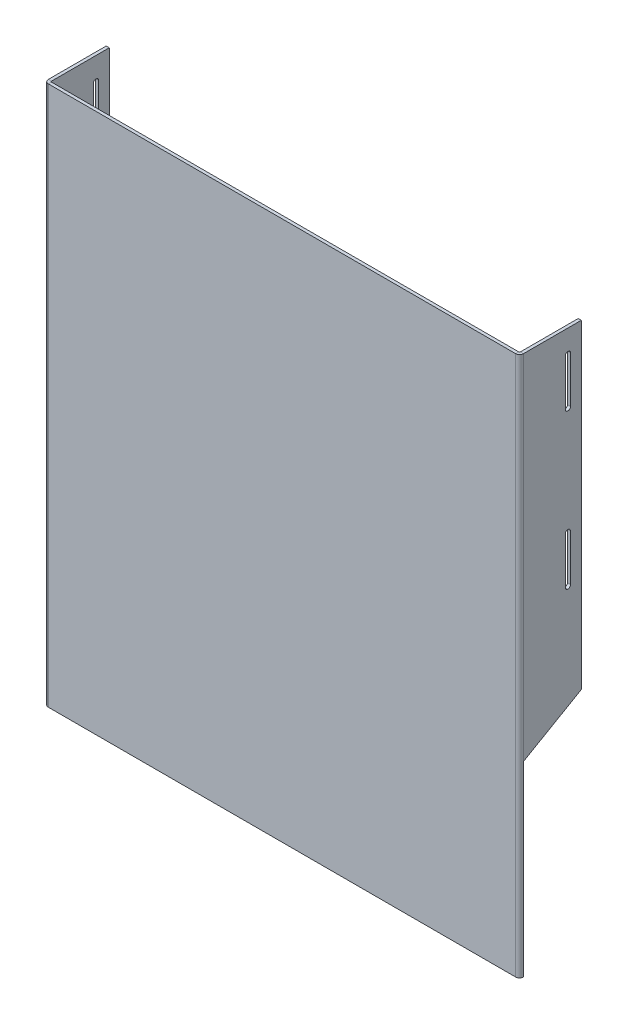
SolidWorks part; units mm, degrees
note: The reader was unsure of these and kept them because the rebuilt part matched: flange length of "Edge-Flange1".
ref_plane "Front Plane" through (0, 0, 0) normal (0, 0, 1) x (1, 0, 0)
ref_plane "Top Plane" through (0, 0, 0) normal (0, 1, 0) x (1, 0, 0)
ref_plane "Right Plane" through (0, 0, 0) normal (1, 0, 0) x (0, 0, -1)
sketch "Sketch1" plane through (0, 0, 0) normal (0, 0, 1) x (1, 0, 0)
  line L1 (0, 0) -> (-303, 0)
  line L2 (0, 0) -> (0, 350)
  line L3 (0, 350) -> (-303, 350)
  line L4 (-303, 0) -> (-303, 350)
  dimension "D1" = 350
  dimension "D2" = 303
base flange "Base-Flange1" sketch "Sketch1" thickness 2 reverse thickness direction no parameters "D1"=2
ref_plane "Plane3" through (-151.5, 0, 0) normal (-1, 0, 0) x (0, 0, 1)
edge flange "Edge-Flange1" sketch "Sketch13" flange angle 90 flange length 40 flange position bend outside bend radius 0.5 thickness 2 relief rectangular parameters "D6"=10
sketch "Sketch13" plane through (-303, 0, -2) normal (1, 0, 0) x (0, -1, 0)
  line L1 (0, 0) -> (-350, 0) construction
  line L2 (-350, 0) -> (-350, 38)
  line L3 (-350, 38) -> (0, 38)
  line L4 (0, 38) -> (0, 0)
  line L5 (0, 0) -> (-350, 0)
bend "EdgeBend1" bend radius 0.5 bend angle 90 parameters "D5"=1
sketch "Sketch15" plane through (-305.5, 0, 0) normal (-1, 0, 0) x (0, 0, 1)
  line L0 (-2.5, 0) -> (-2.5, 121)
  line L1 (-40, 0) -> (-40, 350) construction
  line L3 (-40, 0) -> (-2.5, 0)
  line L4 (-2.5, 0) -> (-2.5, 350) construction
  line L5 (-2.5, 121) -> (-40, 142.6506)
  line L6 (-40, 142.6506) -> (-40, 0)
  dimension "D1" = 229
  dimension "D2" = 60
extrude "Cut-Extrude1" cut sketch "Sketch15" against normal up to next normal cut yes
sketch "Sketch18" plane through (-305.5, 0, 0) normal (-1, 0, 0) x (0, 0, 1)
  line L0 (-31.3559, 235.1372) -> (-31.3559, 205.1372) construction
  line L1 (-29.6559, 235.1372) -> (-29.6559, 205.1372)
  line L2 (-33.0559, 235.1372) -> (-33.0559, 205.1372)
  line L3 (-2.5, 121) -> (-2.5, 350) construction
  line L4 (-40, 350) -> (-2.5, 350) construction
  arc A0 (-29.6559, 235.1372) -> (-33.0559, 235.1372) centre (-31.3559, 235.1372) ccw
  arc A1 (-33.0559, 205.1372) -> (-29.6559, 205.1372) centre (-31.3559, 205.1372) ccw
  point P2 (-31.3559, 220.1372)
  dimension "D2" = 1.7
  dimension "D1" = 28.8559
  dimension "D3" = 129.8628
  dimension "D4" = 30
extrude "Cut-Extrude2" cut sketch "Sketch18" against normal up to next normal cut yes
pattern_linear "LPattern1" count 2 spacing 100 along (0, 1, 0) of "Cut-Extrude2"
mirror "Mirror1" about plane through (-151.5, 0, 0) normal (-1, 0, 0) of "LPattern1", "Cut-Extrude2", "Cut-Extrude1", "Edge-Flange1"
bend "MirrorBend1" bend radius 0.5 bend angle 90 parameters "D5"=2
sketch "Bend-Lines1" [suppressed] plane through (0, 0, 0) normal (0, 1, 0) x (1, 0, 0)
sketch "Bounding-Box1" [suppressed] plane through (0, 0, 0) normal (0, 1, 0) x (1, 0, 0)
sheet metal parameters "Sheet-Metal1" thickness 2 parameters "D1"=2
flat pattern "Flat-Pattern1" [suppressed]
sketch "Bend-Lines2" plane through (0, 0, 0) normal (0, 1, 0) x (1, 0, 0)
sketch3d "Bounding-Box2" [suppressed]
  line L0 (0, 350, 0) -> (0, 0, 0) construction
  line L1 (-300, 350, 0) -> (-300, 0, 0) construction
  line L2 (0, 350, 0) -> (-300, 350, 0) construction
  line L3 (0, 0, 0) -> (-300, 0, 0) construction
sheet metal parameters "Sheet-Metal7" thickness 2 parameters "D1"=2
flat pattern "Flat-Pattern1"
sketch "Bend-Lines2" plane through (0, 0, 0) normal (0, 0, 1) x (1, 0, 0)
  line L0 (-298.6781, 350) -> (-298.6781, 0) construction
  line L1 (-298.6781, 350) -> (-298.6781, 0) construction
sketch3d "Bounding-Box2" [suppressed]
  line L0 (-357.3562, 0, 0) -> (0, 0, 0) construction
  line L1 (-357.3562, 350, 0) -> (0, 350, 0) construction
  line L2 (-357.3562, 0, 0) -> (-357.3562, 350, 0) construction
  line L3 (0, 0, 0) -> (0, 350, 0) construction
bend of the flat pattern "Flatten-<EdgeBend1>1"
sheet metal parameters "Sheet-Metal8" thickness 2 parameters "D1"=2
flat pattern "Flat-Pattern1"
sketch "Bend-Lines2" plane through (0, 0, 0) normal (0, 0, 1) x (1, 0, 0)
  line L0 (-298.6781, 350) -> (-298.6781, 0) construction
  line L1 (-298.6781, 350) -> (-298.6781, 0) construction
sketch3d "Bounding-Box2" [suppressed]
  line L0 (-357.3562, 0, 0) -> (0, 0, 0) construction
  line L1 (-357.3562, 350, 0) -> (0, 350, 0) construction
  line L2 (-357.3562, 0, 0) -> (-357.3562, 350, 0) construction
  line L3 (0, 0, 0) -> (0, 350, 0) construction
bend of the flat pattern "Flatten-<EdgeBend1>1"
sheet metal parameters "Sheet-Metal9" thickness 2 parameters "D1"=2
flat pattern "Flat-Pattern1"
sketch "Bend-Lines2" plane through (0, 0, 0) normal (0, 0, 1) x (1, 0, 0)
  line L0 (-298.6781, 350) -> (-298.6781, 0) construction
  line L1 (-298.6781, 350) -> (-298.6781, 0) construction
sketch3d "Bounding-Box2" [suppressed]
  line L0 (-357.3562, 0, 0) -> (0, 0, 0) construction
  line L1 (-357.3562, 350, 0) -> (0, 350, 0) construction
  line L2 (-357.3562, 0, 0) -> (-357.3562, 350, 0) construction
  line L3 (0, 0, 0) -> (0, 350, 0) construction
bend of the flat pattern "Flatten-<EdgeBend1>1"
sheet metal parameters "Sheet-Metal10" thickness 2 parameters "D1"=2
flat pattern "Flat-Pattern1"
sketch "Bend-Lines2" plane through (0, 0, 0) normal (0, 0, 1) x (1, 0, 0)
  line L0 (-298.6781, 350) -> (-298.6781, 0) construction
  line L1 (-298.6781, 350) -> (-298.6781, 0) construction
sketch3d "Bounding-Box2" [suppressed]
  line L0 (-357.3562, 0, 0) -> (0, 0, 0) construction
  line L1 (-357.3562, 350, 0) -> (0, 350, 0) construction
  line L2 (-357.3562, 0, 0) -> (-357.3562, 350, 0) construction
  line L3 (0, 0, 0) -> (0, 350, 0) construction
bend of the flat pattern "Flatten-<EdgeBend1>1"
sheet metal parameters "Sheet-Metal11" thickness 2 parameters "D1"=2
flat pattern "Flat-Pattern1"
sketch "Bend-Lines2" plane through (0, 0, 0) normal (0, 0, 1) x (1, 0, 0)
  line L0 (-304.1781, 0) -> (-304.1781, 350) construction
  line L1 (-304.1781, 0) -> (-304.1781, 350) construction
  line L2 (1.1781, 0) -> (1.1781, 350) construction
  line L3 (1.1781, 0) -> (1.1781, 350) construction
sketch3d "Bounding-Box2" [suppressed]
  line L0 (-342.8562, 0, 0) -> (39.8562, 0, 0) construction
  line L1 (-342.8562, 350, 0) -> (39.8562, 350, 0) construction
  line L2 (-342.8562, 0, 0) -> (-342.8562, 350, 0) construction
  line L3 (39.8562, 0, 0) -> (39.8562, 350, 0) construction
bend of the flat pattern "Flatten-<EdgeBend1>1"
bend of the flat pattern "Flatten-<MirrorBend1>1"
